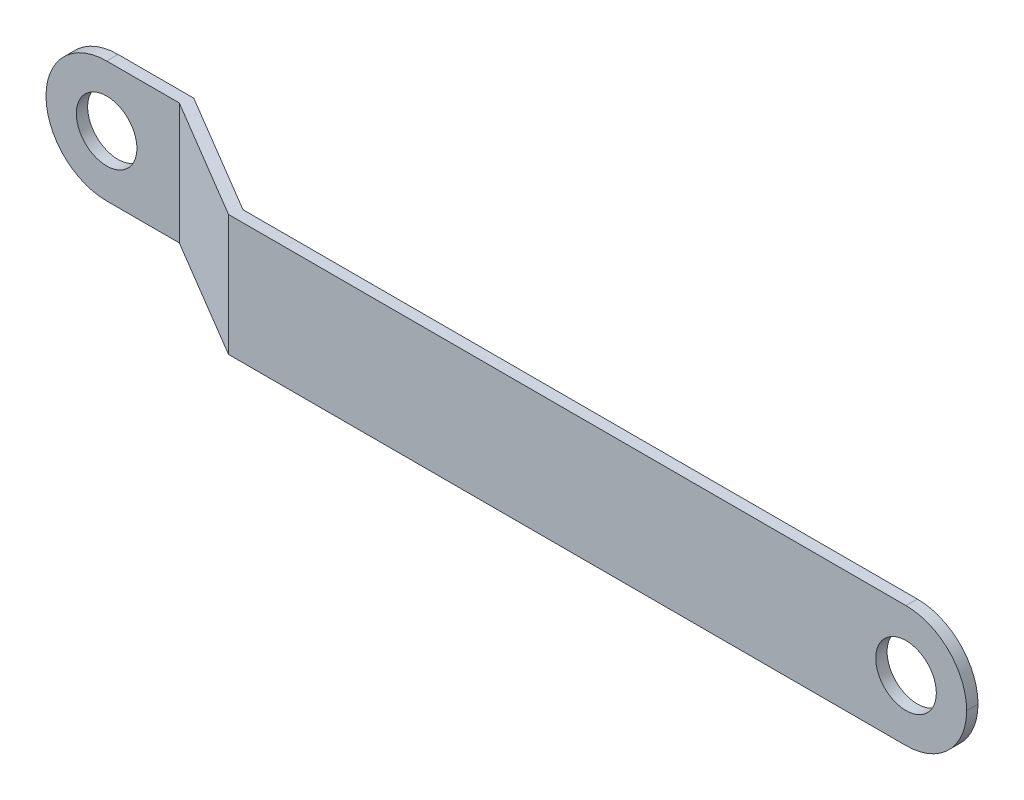
SolidWorks part; units mm, degrees
ref_plane "前视基准面" through (0, 0, 0) normal (0, 0, 1) x (1, 0, 0)
ref_plane "上视基准面" through (0, 0, 0) normal (0, 1, 0) x (1, 0, 0)
ref_plane "右视基准面" through (0, 0, 0) normal (1, 0, 0) x (0, 0, -1)
sketch "草图1" plane through (0, 0, 0) normal (0, 1, 0) x (1, 0, 0)
  line L0 (0, 0) -> (18, 0)
  line L1 (18, 0) -> (34, -9.5)
  line L2 (34, -9.5) -> (131, -9.5)
  dimension "D1" = 9.5
  dimension "D2" = 18
  dimension "D3" = 97
  dimension "D4" = 131
extrude "拉伸-薄壁1" add sketch "草图1" along normal mid plane 16 thin thin type one direction wall 1.5
fillet "圆角1" radius 8 4 edges at (131, -8, 10.25) (131, 8, 10.25) (0, -8, 0.75) (0, 8, 0.75)
sketch "草图2" plane through (0, 0, 1.5) normal (0, 0, 1) x (1, 0, 0)
  circle A0 centre (8, 0) radius 4
  circle A1 centre (123, 0) radius 4
  arc A3 (8, 8) -> (0, 0) centre (8, 0) ccw construction
  arc A4 (131, 0) -> (123, 8) centre (123, 0) ccw construction
  dimension "D1" = 8
extrude "切除-拉伸1" cut sketch "草图2" against normal through all both and the other way through all
